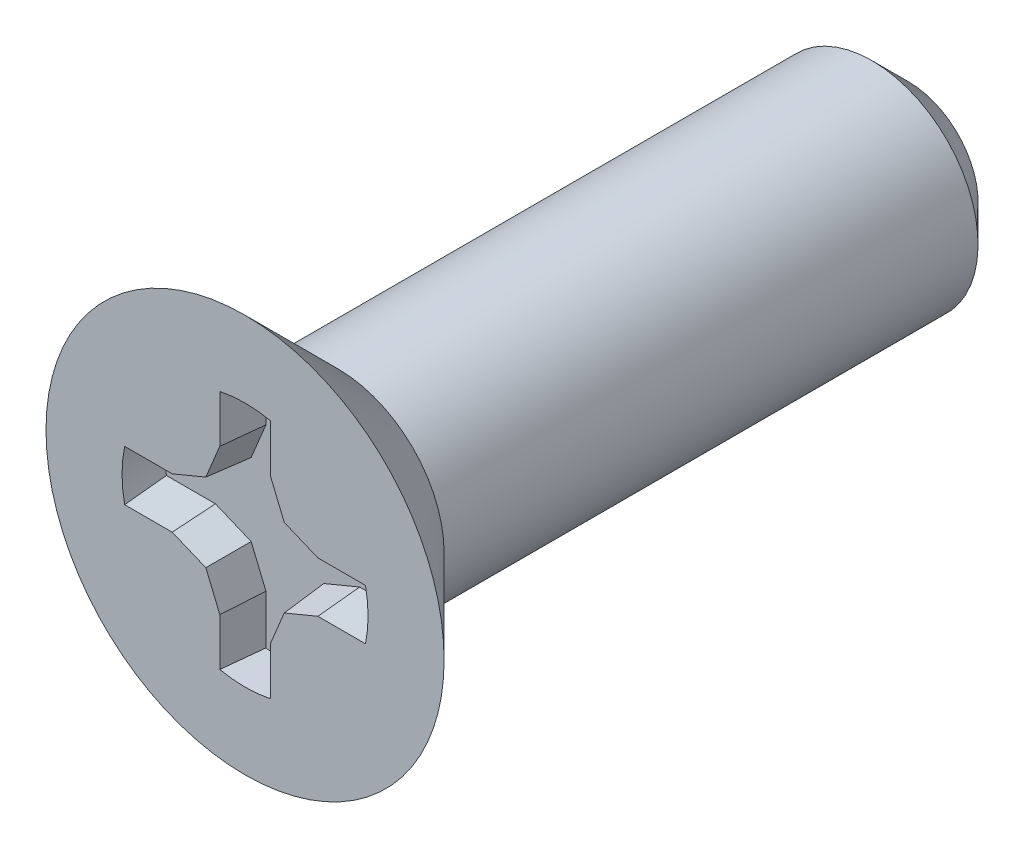
SolidWorks part; units mm, degrees
ref_plane "Front Plane" through (0, 0, 0) normal (0, 0, 1) x (1, 0, 0)
ref_plane "Top Plane" through (0, 0, 0) normal (0, 1, 0) x (1, 0, 0)
ref_plane "Right Plane" through (0, 0, 0) normal (1, 0, 0) x (0, 0, -1)
sketch "Sketch1" plane through (0, 0, 0) normal (1, 0, 0) x (0, 0, -1)
  line L0 (0, 0) -> (-0.96, 0) construction
  line L1 (-0.96, 1.5) -> (-0.96, -1.5) construction
  line L2 (-0.96, 1.5) -> (0, 0.54) construction
  line L3 (-0.96, -1.5) -> (0, -0.54) construction
  line L4 (0, 0.8) -> (0, -0.8) construction
  line L5 (0, 0) -> (4.04, 0) construction
  line L6 (0, 0.8) -> (0.35, 0.8) construction
  line L7 (0, 0.8) -> (-0.26, 0.8) construction
  line L8 (4.04, 0.54) -> (4.04, -0.54) construction
  point P6 (-0.96, 0)
  point P11 (0, 0)
  point P16 (-0.26, 0.8)
  point P17 (2.815, -0.8)
  point P20 (4.04, 0)
  point P21 (-0.48, 0)
  point P22 (2.815, -0.54)
  point P23 (4.04, -0.54)
  point P25 (4.04, 0.54)
  dimension "Head Height" = 0.96
  dimension "Head Diameter" = 3
  dimension "Countersink Angle" = 90
  dimension "Thread OD" = 1.6
  dimension "Length" = 5
  dimension "Thread Pitch" = 0.35
  dimension "D1" = 1.225
sketch "Sketch2" plane through (0, 0, 0) normal (0, 0, 1) x (1, 0, 0)
  line L0 (0.1905, 0.9271) -> (-0.1905, 0.9271) construction
  circle A0 centre (0, 0) radius 0.9271 construction
  point P3 (0, 0.9271)
  point P7 (0, 0.9271)
  dimension "Drive Dia" = 1.8542
  dimension "Drive Width" = 0.381
sketch "Sketch3" plane through (0, 0, 0) normal (1, 0, 0) x (0, 0, -1)
  line L0 (-0.96, 0) -> (-0.96, 1.5)
  line L1 (-0.96, 1.5) -> (-0.26, 0.8)
  line L2 (-0.96, 1.5) -> (0, 0.54) construction
  line L3 (0, 0.8) -> (0.35, 0.8) construction
  line L4 (-0.96, 0) -> (-0.26, 0)
  line L5 (0, 0) -> (-0.96, 0) construction
  line L6 (-0.26, 0) -> (-0.26, 0.8)
revolve "Revolve1" add sketch "Sketch3" angle 360 about L4
sketch "Sketch5" plane through (0, 0, 0) normal (1, 0, 0) x (0, 0, -1)
  line L0 (4.04, 0) -> (-0.26, 0)
  line L1 (0, 0) -> (4.04, 0) construction
  line L2 (-0.26, 0) -> (-0.26, 0.8)
  line L3 (-0.26, 0.8) -> (3.7635, 0.8)
  line L4 (3.7635, 0.8) -> (4.04, 0.5235)
  line L5 (4.04, 0.5235) -> (4.04, 0)
  line L6 (3.7635, 0.8) -> (4.04, 0.8) construction
  line L7 (4.04, 0.8) -> (4.04, 0.5235) construction
  line L8 (0, 0.8) -> (0.35, 0.8) construction
  line L9 (-0.26, -0.8) -> (-0.26, 0.8) construction
  dimension "D1" = 0.2765
revolve "Revolve2" add sketch "Sketch5" angle 360 about L0
sketch "Sketch4" plane through (0, 0, 0.96) normal (0, 0, 1) x (1, 0, 0)
  line L0 (0, 0) -> (0, 0.9271)
  line L1 (0, 0) -> (0.9271, 0)
  line L2 (0, 0) -> (0.5489, 0.5489) construction
  line L3 (0.1905, 0.9073) -> (0.1905, 0.5489)
  line L4 (0.1905, 0.5489) -> (0.1905, 0.1905) construction
  line L5 (0.5489, 0.1905) -> (0.1905, 0.1905) construction
  line L6 (0.9073, 0.1905) -> (0.5489, 0.1905)
  line L7 (0.1905, 0.5489) -> (0.2955, 0.2955)
  line L8 (0.2955, 0.2955) -> (0.5489, 0.1905)
  line L9 (0, 0.9271) -> (0, 1.5) construction
  line L10 (0, 1.5) -> (0, -1.5) construction
  circle A0 centre (0, 0) radius 0.9271 construction
  arc A1 (0, 0.9271) -> (0.1905, 0.9073) centre (0, 0) cw
  arc A2 (0.9271, 0) -> (0.9073, 0.1905) centre (0, 0) ccw
  arc A3 (0.5489, 0.1905) -> (0.1905, 0.5489) centre (0.5489, 0.5489) cw construction
  circle A4 centre (0, 0) radius 1.5 construction
  point P8 (0.2955, 0.2955)
  point P22 (0, -0.9271)
  point P23 (0, 0.9271)
  dimension "D1" = 0.5729
extrude "Cut-Extrude1" cut sketch "Sketch4" against normal blind 0.32 contours L1 A2 L6 L8 L7 L3 A1 L0 region at (0.0131, 0.4635, 0.96)
pattern_circular "CirPattern1" count 4 over 360 about axis through (0, 0, 0) along (0, 0, -1) of "Cut-Extrude1"
draft "Draft2" type of draft neutral plane draft angle 5 faces to draft 16 face at (-0.7281, 0.1905, 0.8) face at (-0.4222, 0.243, 0.8) face at (-0.243, 0.4222, 0.8) face at (-0.1905, 0.7281, 0.8) face at (0.1905, 0.7281, 0.8) face at (0.243, 0.4222, 0.8) face at (0.4222, 0.243, 0.8) face at (0.7281, 0.1905, 0.8) face at (0.7281, -0.1905, 0.8) face at (0.4222, -0.243, 0.8) face at (0.243, -0.4222, 0.8) face at (0.1905, -0.7281, 0.8) face at (-0.1905, -0.7281, 0.8) face at (-0.243, -0.4222, 0.8) face at (-0.4222, -0.243, 0.8) face at (-0.7281, -0.1905, 0.8) neutral plane through (0, 0, 0.96) neutral plane normal (0, 0, 1) parameters "D1"=5
ref_plane "Plane1" through (0, 0, 0.26) normal (0, 0, -1) x (-1, 0, 0)
split "Split1" trim tools "Plane1" bodies to split 107 105 resulting bodies 108 109
sketch "Sketch6" plane through (0, 0, -4.04) normal (0, 0, 1) x (1, 0, 0)
  circle A1 centre (0, 0) radius 0.8
  circle A2 centre (0, 0) radius 0.8
  dimension "D1" = 0
curve "Helix/Spiral1" pitch 0.35 height 5 turns 14.2857
sketch "Sketch7" plane through (0, 0, 0) normal (1, 0, 0) x (0, 0, -1)
  line L0 (4.0181, 0.8379) -> (4.3681, 0.8379) construction
  line L1 (4.0181, 0.8379) -> (4.1931, 0.5348) construction
  line L2 (4.1931, 0.5348) -> (4.3681, 0.8379) construction
  line L3 (4.1712, 0.5727) -> (4.215, 0.5727) construction
  line L4 (4.04, 0.8) -> (4.3463, 0.8) construction
  line L5 (4.1931, 0.8) -> (4.1931, 0.8379) construction
  line L6 (4.1931, 0.5727) -> (4.1931, 0.5348) construction
  line L7 (4.1931, 0.8189) -> (4.0291, 0.8189) construction
  line L10 (4.215, 0.5727) -> (4.1712, 0.5727)
  line L11 (4.0291, 0.8189) -> (4.1712, 0.5727)
  line L12 (4.0291, 0.8189) -> (4.3572, 0.8189)
  line L13 (4.3572, 0.8189) -> (4.215, 0.5727)
  dimension "D1" = 0.35
  dimension "D2" = 0.0437
sweep "Cut-Sweep1" [suppressed] cut profiles "Sketch7" path "Helix/Spiral1"
combine bodies "Combine1" operation type add bodies to combine 109 108
ref_plane "Plane2" through (0, 0, 0.26) normal (0, 0, 1) x (1, 0, 0)
sketch "Sketch8" plane through (0, 0, 0.26) normal (0, 0, 1) x (1, 0, 0)
  circle A0 centre (0, 0) radius 0.8
extrude "Boss-Extrude1" add sketch "Sketch8" against normal up to vertex (0.26 mm away) draft 45 up to point (0, 0.54, 0)
equation "\"D1@Sketch5\" = \"Thread Pitch@Sketch1\" * .79"
equation "\"D4@Helix/Spiral1\" = \"Thread Pitch@Sketch1\""
equation "\"D3@Helix/Spiral1\"=\"Length@Sketch1\""
equation "\"D1@Sketch7\" = \"Thread Pitch@Sketch1\""
equation "\"D2@Sketch7\" = \"Thread Pitch@Sketch1\" / 8"
equation "\"D1@Sketch1\"=\"Thread Pitch@Sketch1\"*3.5"
equation "\"D1@Cut-Extrude1\"=\"Head Height@Sketch1\"/3"
